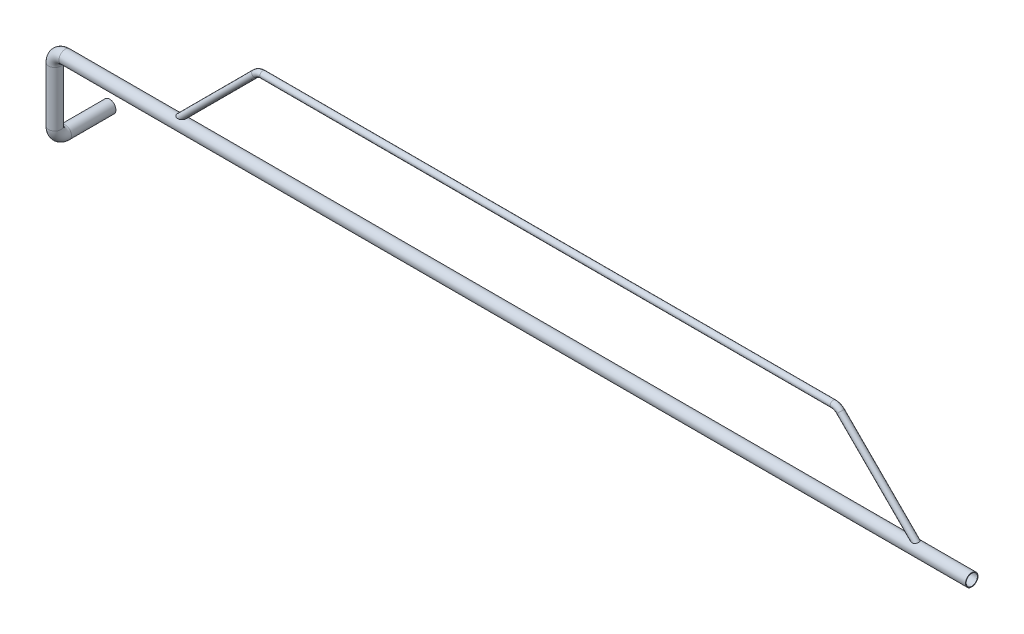
SolidWorks part; units mm, degrees
ref_plane "Plano frontal" through (0, 0, 0) normal (0, 0, 1) x (1, 0, 0)
ref_plane "Plano superior" through (0, 0, 0) normal (0, 1, 0) x (1, 0, 0)
ref_plane "Plano direito" through (0, 0, 0) normal (1, 0, 0) x (0, 0, -1)
sketch3d "3DSketch1"
  line L0 (-24893.0062, -8356.2045, 39090.2493) -> (-29246.5547, -8356.2045, 39090.2493)
  line L3 (-29296.5547, -8406.2045, 39090.2493) -> (-29296.5547, -8670.5186, 39090.2493)
  line L4 (-29296.5547, -8720.5186, 39040.2493) -> (-29296.5547, -8720.5186, 38826.8902)
  line L5 (-29296.5547, -8720.5186, 38826.8902) -> (-29296.5547, -8720.5186, 38797.8902) construction
  arc A0 (-29296.5547, -8720.5186, 39040.2493) -> (-29296.5547, -8670.5186, 39090.2493) centre (-29296.5547, -8670.5186, 39040.2493) ccw
  arc A1 (-29296.5547, -8406.2045, 39090.2493) -> (-29246.5547, -8356.2045, 39090.2493) centre (-29246.5547, -8406.2045, 39090.2493) ccw
  point P12 (-29296.5547, -8720.5186, 39090.2493)
  point P13 (-29346.5547, -8670.5186, 39040.2493)
  point P16 (-29296.5547, -8356.2045, 39090.2493)
  point P17 (-29246.5547, -8406.2045, 39040.2493)
  dimension "D1" = 50
sweep "Sweep-Thin1" add path "3DSketch1" circular profile diameter 60 parameters "D1"=3, "D3"=60
sketch3d "3DSketch2"
  line L0 (-25137.3745, -8356.2045, 39090.2493) -> (-25522.7298, -7970.8492, 39090.2493)
  line L1 (-24893.0062, -8356.2045, 39090.2493) -> (-29246.5547, -8356.2045, 39090.2493) construction
  line L2 (-25558.0851, -7956.2045, 39090.2493) -> (-28297.4869, -7956.2045, 39090.2493)
  line L3 (-28332.8423, -7970.8492, 39090.2493) -> (-28718.1976, -8356.2045, 39090.2493)
  line L6 (-25693.0803, -7956.2045, 39090.2493) -> (-25693.0803, -8356.2045, 39090.2493) construction
  arc A0 (-28297.4869, -7956.2045, 39090.2493) -> (-28332.8423, -7970.8492, 39090.2493) centre (-28297.4869, -8006.2045, 39090.2493) ccw
  arc A1 (-25558.0851, -7956.2045, 39090.2493) -> (-25522.7298, -7970.8492, 39090.2493) centre (-25558.0851, -8006.2045, 39090.2493) ccw
  point P17 (-28318.1976, -7956.2045, 39090.2493)
  point P18 (-28297.4869, -8006.2045, 39140.2493)
  point P21 (-25537.3745, -7956.2045, 39090.2493)
  point P22 (-25558.0851, -8006.2045, 39040.2493)
  dimension "D4" = 50
  dimension "D1" = 135
  dimension "D2" = 135
  dimension "D3" = 400
sweep "Sweep-Thin2" add path "3DSketch2" circular profile diameter 30 parameters "D1"=3, "D3"=30
